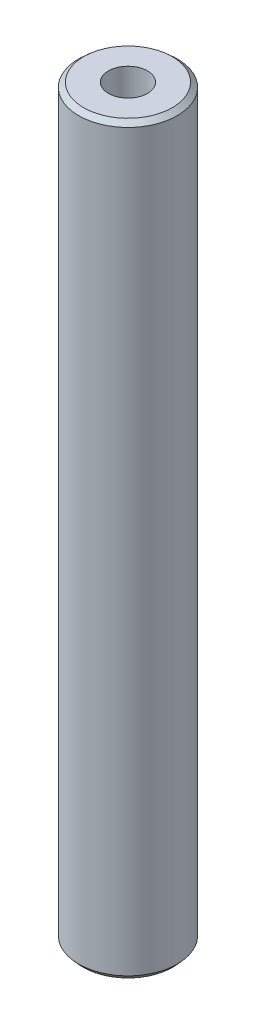
SolidWorks part; units mm, degrees
ref_plane "Front Plane" through (0, 0, 0) normal (0, 0, 1) x (1, 0, 0)
ref_plane "Top Plane" through (0, 0, 0) normal (0, 1, 0) x (1, 0, 0)
ref_plane "Right Plane" through (0, 0, 0) normal (1, 0, 0) x (0, 0, -1)
sketch "Sketch1" plane through (0, 0, 0) normal (0, 1, 0) x (1, 0, 0)
  circle A0 centre (0, 0) radius 30
  dimension "SHAFT_OD" = 60
extrude "Boss-Extrude1" add sketch "Sketch1" along normal blind 453.1487
sketch "Sketch2" plane through (0, 0, 0) normal (0, 1, 0) x (1, 0, 0)
  circle A0 centre (0, 0) radius 11.8984
  dimension "BORE_D" = 23.7968
extrude "Cut-Extrude1" cut sketch "Sketch2" along normal through all
chamfer "Chamfer1" distance 2.7007 angle 48.361 2 edges at (0, 453.1487, 30) (0, 0, 30) first distance on face at (0, 453.1487, 30) first distance on face at (0, 0, 11.8984)
